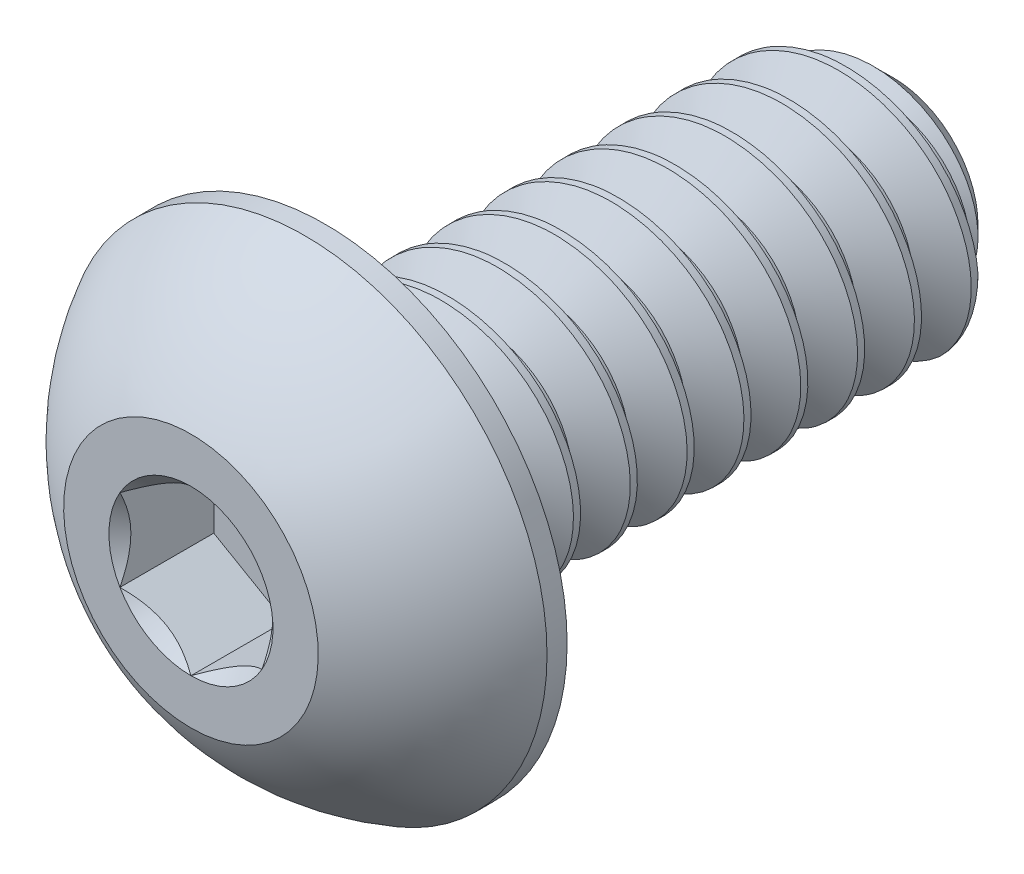
SolidWorks part; units mm, degrees
ref_plane "Front" through (0, 0, 0) normal (0, 0, 1) x (1, 0, 0)
ref_plane "Top" through (0, 0, 0) normal (0, 1, 0) x (1, 0, 0)
ref_plane "Right" through (0, 0, 0) normal (1, 0, 0) x (0, 0, -1)
sketch "Sketch1" plane through (0, 0, 0) normal (1, 0, 0) x (0, 0, -1)
  line L2 (1.4986, 1.4224) -> (7.8486, 1.4224)
  line L3 (7.8486, 1.4224) -> (7.8486, 0)
  line L4 (7.8486, 0) -> (1.4986, 0)
  line L6 (1.2738, 2.7051) -> (1.4986, 2.7051) construction
  line L7 (7.8486, 1.4224) -> (7.8486, -1.4224) construction
  line L8 (0, 0) -> (1.4986, 0) construction
  line L9 (1.4986, 2.7051) -> (1.4986, -2.7051) construction
  line L11 (1.4986, 1.4224) -> (1.4986, 0)
  line L13 (0, 0.7937) -> (0, -0.7937) construction
  line L14 (0, 0.7937) -> (0, 1.4224) construction
  arc A3 (0, 1.4224) -> (1.2738, 2.7051) centre (2.7151, 0) cw construction
  dimension "D1" = 0.2248
revolve "Revolve1" add sketch "Sketch1" angle 360 mid plane about L4
sketch "Sketch3" plane through (0, 0, -7.8486) normal (0, 0, -1) x (-1, 0, 0)
  circle A0 centre (0, 0) radius 1.4224
curve "Helix/Spiral1" pitch 0.635 height 6.985 radius 1.4224 centre (0, 0, -7.8486) axis (0, 0, 1) start towards (0, 1, 0)
sketch "Sketch2" plane through (0, 0, 0) normal (1, 0, 0) x (0, 0, -1)
  line L0 (7.8486, 1.4224) -> (8.4042, 1.4224)
  line L1 (8.4042, 1.4224) -> (8.1661, 1.01)
  line L2 (8.1661, 1.01) -> (8.0867, 1.01)
  line L3 (8.0867, 1.01) -> (7.8486, 1.4224)
  line L4 (7.9677, 1.2162) -> (8.2852, 1.2162) construction
  dimension "D1" = 60
  dimension "D2" = 0.0794
  dimension "D3" = 0.3175
chamfer "Chamfer1" distance 0.4763 angle 45 1 edges at (0, 1.4224, -7.8486)
sweep "Cut-Sweep1" cut profiles "Sketch2" path "Helix/Spiral1" align with end faces yes
sketch "Sketch7" plane through (0, 0, 0) normal (1, 0, 0) x (0, 0, -1)
  line L6 (1.2738, 2.7051) -> (1.4986, 2.7051) construction
  line L8 (0, 0) -> (1.4986, 0) construction
  line L11 (1.4986, 2.7051) -> (1.4986, -2.7051) construction
  line L12 (1.2738, 2.7051) -> (1.4986, 2.7051)
  line L13 (0, 0) -> (1.4986, 0)
  line L14 (0, 0.7937) -> (0, -0.7937) construction
  line L15 (1.4986, 2.7051) -> (1.4986, 0)
  line L16 (0, 1.4224) -> (0, 0)
  arc A2 (1.2738, 2.7051) -> (0, 1.4224) centre (2.7151, 0) ccw construction
  arc A3 (1.2738, 2.7051) -> (0, 1.4224) centre (2.7151, 0) ccw
revolve "Revolve2" add sketch "Sketch7" angle 360 mid plane about L13
sketch "Sketch5" plane through (0, 0, 0) normal (0, 0, 1) x (1, 0, 0)
  line L1 (0.7937, -0.4583) -> (0.7937, 0.4583)
  line L2 (0.7937, 0.4583) -> (0, 0.9165)
  line L3 (0, 0.9165) -> (-0.7937, 0.4583)
  line L4 (-0.7937, 0.4583) -> (-0.7937, -0.4583)
  line L5 (-0.7937, -0.4583) -> (0, -0.9165)
  line L6 (0, -0.9165) -> (0.7937, -0.4583)
  circle A0 centre (0, 0) radius 0.7937 construction
extrude "Cut-Extrude2" cut sketch "Sketch5" against normal blind 1.049
sketch "Sketch6" plane through (0, 0, 0) normal (0, 0, 1) x (1, 0, 0)
  circle A0 centre (0, 0) radius 0.9165
extrude "Cut-Extrude3" cut sketch "Sketch6" against normal blind 1.049 draft 45
sketch "Sketch9" [suppressed] plane through (0, 0, -1.4986) normal (0, 0, 1) x (1, 0, 0)
  circle A2 centre (0, 0) radius 1.4224
extrude "Boss-Extrude2" [suppressed] add sketch "Sketch9" against normal offset from surface (12.7 mm away) 31.75 up to face at (0, 0.9461, -7.8486)
sketch "Sketch10" plane through (0, 0, 0) normal (1, 0, 0) x (0, 0, -1)
  line L0 (7.8486, 1.4224) -> (7.8486, -1.4224) construction
  point P0 (6.8961, -1.4224)
  dimension "D1" = 0.9525
equation "\"D3@Helix/Spiral1\" = \"Lg@Sketch1\" + \"D4@Helix/Spiral1\""
equation "\"D2@Sketch2\" = \"D4@Helix/Spiral1\" * .125"
equation "\"D3@Sketch2\" = \"D4@Helix/Spiral1\" * .5"
equation "\"D1@Chamfer1\" = \"D4@Helix/Spiral1\" * .75"
equation "\"D1@Cut-Extrude2\" = \"Head Ht@Sketch1\" * .7"
equation "\"D1@Sketch1\" = \"Head Ht@Sketch1\" * .15"
equation "\"D1@Sketch10\" = \"D4@Helix/Spiral1\" * 1.5"
equation "\"D1@Cut-Extrude3\" = \"D1@Cut-Extrude2\""
